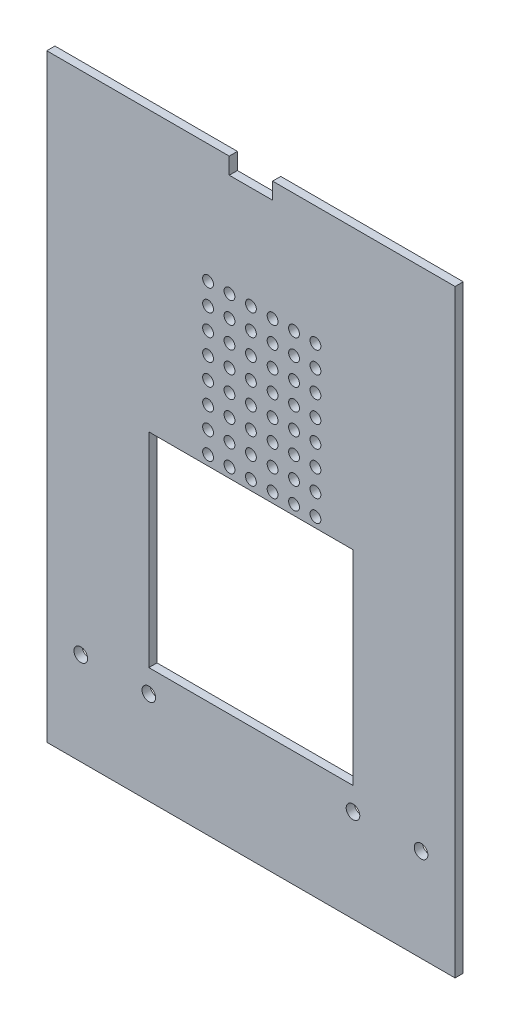
SolidWorks part; units mm, degrees
ref_plane "Front Plane" through (0, 0, 0) normal (0, 0, 1) x (1, 0, 0)
ref_plane "Top Plane" through (0, 0, 0) normal (0, 1, 0) x (1, 0, 0)
ref_plane "Right Plane" through (0, 0, 0) normal (1, 0, 0) x (0, 0, -1)
sketch "Sketch1" plane through (0, 0, 0) normal (0, 0, 1) x (1, 0, 0)
  line L1 (-76.2, 146.05) -> (76.2, 146.05)
  line L2 (-76.2, 146.05) -> (-76.2, -146.05)
  line L3 (-76.2, -146.05) -> (76.2, -146.05)
  line L4 (76.2, 146.05) -> (76.2, -146.05)
  line L5 (-76.2, 146.05) -> (76.2, -146.05) construction
  line L6 (-76.2, -146.05) -> (76.2, 146.05) construction
  point P0 (0, 0)
  dimension "D1" = 152.4
  dimension "D2" = 292.1
extrude "Boss-Extrude1" add sketch "Sketch1" along normal blind 3.048
sketch "Sketch2" plane through (0, 0, 0) normal (0, 0, 1) x (1, 0, 0)
  line L1 (-76.2, -146.05) -> (76.2, -146.05) construction
  line L2 (-76.2, -146.05) -> (76.2, -146.05) construction
  line L3 (8.0869, 109.0549) -> (-8.0869, 109.0549)
  line L4 (8.0869, 109.0549) -> (8.0869, 76.3651)
  line L5 (8.0869, 76.3651) -> (-8.0869, 76.3651)
  line L6 (-8.0869, 109.0549) -> (-8.0869, 76.3651)
  line L7 (8.0869, 109.0549) -> (-8.0869, 76.3651) construction
  line L8 (8.0869, 76.3651) -> (-8.0869, 109.0549) construction
  line L9 (-38.1, -21.59) -> (38.1, -21.59)
  line L10 (-38.1, -21.59) -> (-38.1, -97.79)
  line L11 (-38.1, -97.79) -> (38.1, -97.79)
  line L12 (38.1, -21.59) -> (38.1, -97.79)
  line L13 (-38.1, -21.59) -> (38.1, -97.79) construction
  line L14 (-38.1, -97.79) -> (38.1, -21.59) construction
  circle A1 centre (0, 92.71) radius 10.7315
  circle A2 centre (0, 38.1) radius 2.0193
  circle A3 centre (0, 30.1) radius 2.0193
  circle A4 centre (0, 22.1) radius 2.0193
  circle A5 centre (0, 14.1) radius 2.0193
  circle A6 centre (0, 6.1) radius 2.0193
  circle A7 centre (0, -1.9) radius 2.0193
  circle A8 centre (0, -9.9) radius 2.0193
  circle A9 centre (0, -17.9) radius 2.0193
  circle A10 centre (-8, 38.1) radius 2.0193
  circle A11 centre (-16, 38.1) radius 2.0193
  circle A12 centre (-8, 30.1) radius 2.0193
  circle A13 centre (-16, 30.1) radius 2.0193
  circle A14 centre (-8, 22.1) radius 2.0193
  circle A15 centre (-16, 22.1) radius 2.0193
  circle A16 centre (-8, 14.1) radius 2.0193
  circle A17 centre (-16, 14.1) radius 2.0193
  circle A18 centre (-8, 6.1) radius 2.0193
  circle A19 centre (-16, 6.1) radius 2.0193
  circle A20 centre (-8, -1.9) radius 2.0193
  circle A21 centre (-16, -1.9) radius 2.0193
  circle A22 centre (-8, -9.9) radius 2.0193
  circle A23 centre (-16, -9.9) radius 2.0193
  circle A24 centre (-8, -17.9) radius 2.0193
  circle A25 centre (-16, -17.9) radius 2.0193
  circle A26 centre (24.0869, 14.1) radius 2.0193
  circle A27 centre (8.0869, 14.1) radius 2.0193
  circle A28 centre (8.0869, -17.9) radius 2.0193
  circle A29 centre (24.0869, 6.1) radius 2.0193
  circle A30 centre (16.0869, 6.1) radius 2.0193
  circle A31 centre (8.0869, -1.9) radius 2.0193
  circle A32 centre (8.0869, 30.1) radius 2.0193
  circle A33 centre (24.0869, 22.1) radius 2.0193
  circle A34 centre (24.0869, -1.9) radius 2.0193
  circle A35 centre (24.0869, -9.9) radius 2.0193
  circle A36 centre (8.0869, 6.1) radius 2.0193
  circle A37 centre (16.0869, 22.1) radius 2.0193
  circle A38 centre (8.0869, 22.1) radius 2.0193
  circle A39 centre (8.0869, -9.9) radius 2.0193
  circle A40 centre (24.0869, -17.9) radius 2.0193
  circle A41 centre (16.0869, 14.1) radius 2.0193
  circle A42 centre (16.0869, -17.9) radius 2.0193
  circle A43 centre (16.0869, 30.1) radius 2.0193
  circle A44 centre (24.0869, 30.1) radius 2.0193
  circle A45 centre (16.0869, -9.9) radius 2.0193
  circle A46 centre (16.0869, -1.9) radius 2.0193
  circle A47 centre (16.0869, 38.1) radius 2.0193
  circle A48 centre (8.0869, 38.1) radius 2.0193
  circle A49 centre (24.0869, 38.1) radius 2.0193
  point P2 (0, -59.69)
  point P111 (0, 0)
  point P112 (0, 0)
  point P113 (0, 0)
  point P114 (0, 0)
  point P115 (0, 0)
  point P116 (0, 0)
  point P117 (0, 0)
  point P118 (0, 0)
  point P119 (0, 0)
  dimension "D3" = 21.463
  dimension "D5" = 4.0386
  dimension "D7" = 184.15
  dimension "D2" = 86.36
  dimension "D4" = 152.4
  dimension "D8" = 16.1738
  dimension "D9" = 32.6898
  dimension "D11" = 76.2
  dimension "D12" = 76.2
  dimension "D6" = 3
  dimension "D10" = 8
extrude "Cut-Extrude1" cut sketch "Sketch2" along normal through all contours A13 | A19 | A18 | A20 | A24 | A39 | A31 | L3 L6 L5 L4 | A1 | A3 | A2 | A4 | A5 | A6 | A7 | A8 | A9 | A10 | A12 | A11 | A15 | A14 | A17 | A16 | A21 | A23 | A22 | A25 | L11 L12 L9 L10 | A42 | A40 | A28 | A36 | A27 | A38 | A32 | A48 | A47 | A49 | A43 | A37 | A41 | A30 | A46 | A45 | A35 | A34 | A29 | A26 | A33 | A44 region at (-16, 30.1, 0) region at (-8, 6.1, 0) region at (-16, 6.1, 0) region at (-8, -1.9, 0) region at (-8, -17.9, 0) region at (8.0869, -1.9, 0) region at (8.0869, -9.9, 0)
sketch "Sketch4" plane through (0, 0, 0) normal (0, 0, 1) x (1, 0, 0)
  line L1 (76.2, 146.05) -> (-76.2, 146.05)
  line L2 (76.2, 146.05) -> (76.2, 82.55)
  line L3 (76.2, 82.55) -> (-76.2, 82.55)
  line L4 (-76.2, 146.05) -> (-76.2, 82.55)
  point P5 (20.32, 146.05)
  dimension "D1" = 152.4
  dimension "D2" = 63.5
extrude "Cut-Extrude2" cut sketch "Sketch4" along normal through all
sketch "Sketch5" plane through (0, 0, 0) normal (0, 0, -1) x (-1, 0, 0)
  line L0 (76.2, -146.05) -> (-76.2, -146.05) construction
  line L1 (-76.2, -146.05) -> (-76.2, 82.55) construction
  line L2 (0, 1.6764) -> (0, -1.6764) construction
  circle A0 centre (-38.1, -106.299) radius 2.54
  circle A2 centre (-63.5, -106.299) radius 2.54
  circle A3 centre (63.5, -106.299) radius 2.54
  circle A4 centre (38.1, -106.299) radius 2.54
  dimension "D1" = 5.08
  dimension "D2" = 39.751
  dimension "D3" = 25.4
  dimension "D4" = 12.7
extrude "Cut-Extrude3" cut sketch "Sketch5" against normal through all
sketch "Sketch6" plane through (0, 0, 0) normal (0, 0, -1) x (-1, 0, 0)
  line L0 (76.2, 82.55) -> (76.2, -146.05) construction
  line L1 (-76.2, -146.05) -> (76.2, -146.05)
  line L2 (-76.2, -146.05) -> (-76.2, -140.97)
  line L3 (-76.2, -140.97) -> (76.2, -140.97)
  line L4 (76.2, -146.05) -> (76.2, -140.97)
  dimension "D1" = 5.08
extrude "Cut-Extrude4" cut sketch "Sketch6" against normal through all
equation "\"thickness_acrylic0.1\"=0.1in"
equation "\"motor offset\"=6mm"
equation "\"thickness0.25\"=0.225in"
equation "\"thickness0.125\"=0.122in"
